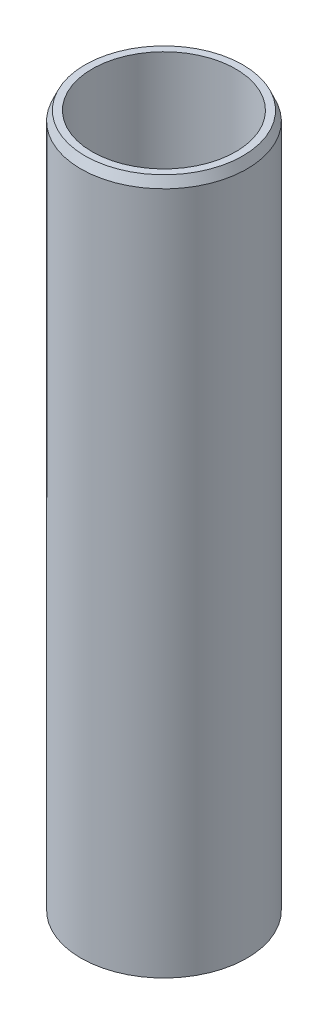
SolidWorks part; units mm, degrees
ref_plane "Front Plane" through (0, 0, 0) normal (0, 0, 1) x (1, 0, 0)
ref_plane "Top Plane" through (0, 0, 0) normal (0, 1, 0) x (1, 0, 0)
ref_plane "Right Plane" through (0, 0, 0) normal (1, 0, 0) x (0, 0, -1)
sketch "Sketch1" plane through (0, 0, 0) normal (0, 1, 0) x (1, 0, 0)
  circle A0 centre (0, 0) radius 52.5
  dimension "SHAFT_OD" = 105
extrude "Boss-Extrude1" add sketch "Sketch1" along normal blind 440.6265
sketch "Sketch2" plane through (0, 0, 0) normal (0, 1, 0) x (1, 0, 0)
  circle A0 centre (0, 0) radius 45.394
  dimension "BORE_D" = 90.7879
extrude "Cut-Extrude1" cut sketch "Sketch2" along normal through all
chamfer "Chamfer1" distance 5.8842 angle 23.752 2 edges at (0, 440.6265, 52.5) (0, 0, 52.5) first distance on face at (0, 440.6265, 52.5) first distance on face at (0, 0, 45.394)
